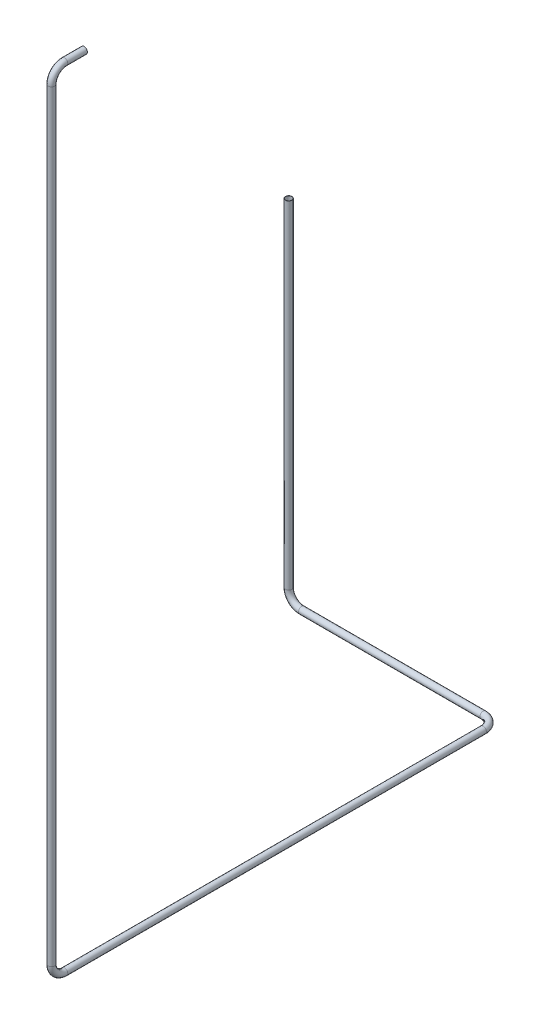
SolidWorks part; units mm, degrees
ref_plane "Plano frontal" through (0, 0, 0) normal (0, 0, 1) x (1, 0, 0)
ref_plane "Plano superior" through (0, 0, 0) normal (0, 1, 0) x (1, 0, 0)
ref_plane "Plano direito" through (0, 0, 0) normal (1, 0, 0) x (0, 0, -1)
sketch3d "3DSketch1"
  line L0 (-33126.1177, -14247.0136, 43090.4702) -> (-33126.1177, -14247.0136, 43140.4702) construction
  line L1 (-33126.1177, -14247.0136, 43140.4702) -> (-33126.1177, -14247.0136, 43230.4702)
  line L2 (-33126.1177, -14307.0136, 43290.4702) -> (-33126.1177, -17802.3318, 43290.4702)
  line L3 (-33126.1177, -17862.3318, 43230.4702) -> (-33126.1177, -17862.3318, 41310.1351)
  line L4 (-33186.1177, -17862.3318, 41250.1351) -> (-34018.2843, -17862.3318, 41250.1351)
  line L6 (-34078.2843, -17802.3318, 41250.1351) -> (-34078.2843, -16256.7026, 41250.1351)
  arc A1 (-34078.2843, -17802.3318, 41250.1351) -> (-34018.2843, -17862.3318, 41250.1351) centre (-34018.2843, -17802.3318, 41250.1351) ccw
  arc A2 (-33186.1177, -17862.3318, 41250.1351) -> (-33126.1177, -17862.3318, 41310.1351) centre (-33186.1177, -17862.3318, 41310.1351) ccw
  arc A3 (-33126.1177, -17862.3318, 43230.4702) -> (-33126.1177, -17802.3318, 43290.4702) centre (-33126.1177, -17802.3318, 43230.4702) ccw
  arc A4 (-33126.1177, -14307.0136, 43290.4702) -> (-33126.1177, -14247.0136, 43230.4702) centre (-33126.1177, -14307.0136, 43230.4702) ccw
  point P4 (0, 0, 0)
  point P5 (0, 0, 0)
  point P9 (0, 0, 0)
  point P13 (-34078.2843, -17862.3318, 41250.1351)
  point P14 (-34018.2843, -17802.3318, 41310.1351)
  point P17 (-33126.1177, -17862.3318, 41250.1351)
  point P18 (-33186.1177, -17922.3318, 41310.1351)
  point P21 (-33126.1177, -17862.3318, 43290.4702)
  point P22 (-33186.1177, -17802.3318, 43230.4702)
  point P25 (-33126.1177, -14247.0136, 43290.4702)
  point P26 (-33186.1177, -14307.0136, 43230.4702)
  point P27 (0, 0, 0)
  point P28 (0, 0, 0)
  point P29 (0, 0, 0)
  point P30 (0, 0, 0)
  point P31 (0, 0, 0)
  point P33 (-34018.2843, -17862.3318, 41379.3291)
  dimension "D1" = 60
sweep "Sweep-Thin1" add path "3DSketch1" circular profile diameter 30 parameters "D1"=1, "D3"=30
